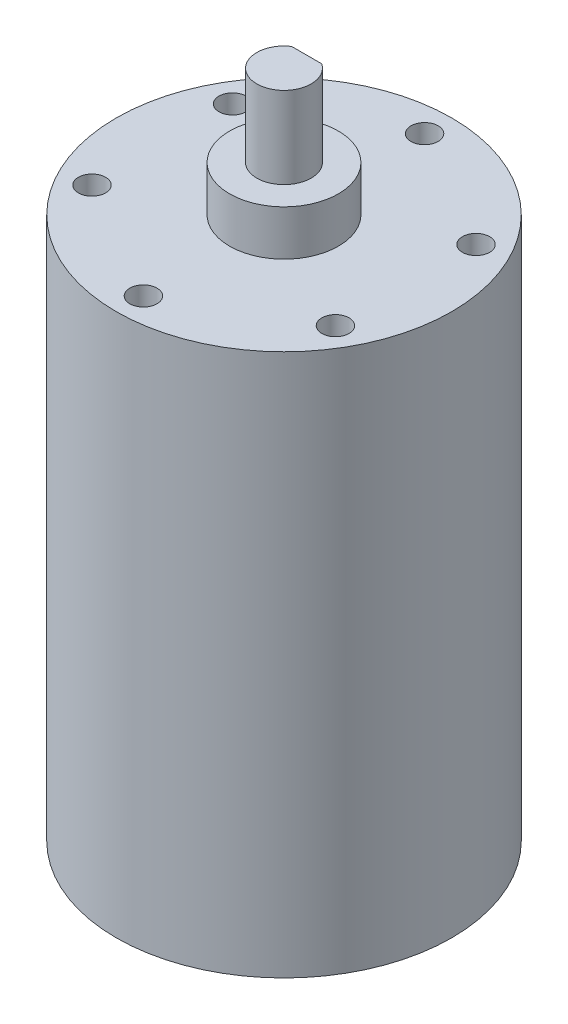
SolidWorks part; units mm, degrees
ref_plane "Front Plane" through (0, 0, 0) normal (0, 0, 1) x (1, 0, 0)
ref_plane "Top Plane" through (0, 0, 0) normal (0, 1, 0) x (1, 0, 0)
ref_plane "Right Plane" through (0, 0, 0) normal (1, 0, 0) x (0, 0, -1)
sketch "Sketch1" plane through (0, 0, 0) normal (0, 1, 0) x (1, 0, 0)
  circle A0 centre (0, 0) radius 18.5
  dimension "D1" = 37
extrude "Boss-Extrude1" add sketch "Sketch1" along normal blind 59.8
sketch "Sketch2" plane through (0, 59.8, 0) normal (0, 1, 0) x (1, 0, 0)
  line L0 (-1.6583, 2.5) -> (1.6583, 2.5)
  circle A0 centre (0, 0) radius 6
  circle A1 centre (0, 0) radius 3
  circle A2 centre (0, 0) radius 15.5 construction
  circle A3 centre (0, 15.5) radius 1.5
  circle A4 centre (13.4234, 7.75) radius 1.5
  circle A5 centre (13.4234, -7.75) radius 1.5
  circle A6 centre (0, -15.5) radius 1.5
  circle A7 centre (-13.4234, -7.75) radius 1.5
  circle A8 centre (-13.4234, 7.75) radius 1.5
  point P6 (0, -3)
  point P23 (0, 0)
  dimension "D1" = 12
  dimension "D3" = 6
  dimension "D4" = 31
  dimension "D5" = 3
  dimension "D2" = 5.5
  dimension "D6" = 6
extrude "Boss-Extrude2" add sketch "Sketch2" along normal blind 5 contours A0 A1 | L0 A1 | L0 A1 region at (0, 59.8, -2.7015) region at (0, 59.8, 0.112) region at (-5.8303, 59.8, 0)
extrude "Boss-Extrude3" add sketch "Sketch2<3>" along normal blind 14 contours L0 A1 region at (0, 59.8, 0.112)
sketch "Sketch2<3>" plane through (0, 59.8, 0) normal (0, 1, 0) x (1, 0, 0) same geometry as "Sketch2"
extrude "Cut-Extrude1" cut sketch "Sketch2<5>" against normal blind 5 contours A8 | A3 | A4 | A5 | A6 | A7 region at (0, 59.8, -15.5) region at (13.4234, 59.8, -7.75) region at (13.4234, 59.8, 7.75) region at (0, 59.8, 15.5) region at (-13.4234, 59.8, 7.75) region at (-13.4234, 59.8, -7.75)
sketch "Sketch2<5>" plane through (0, 59.8, 0) normal (0, 1, 0) x (1, 0, 0) same geometry as "Sketch2"
